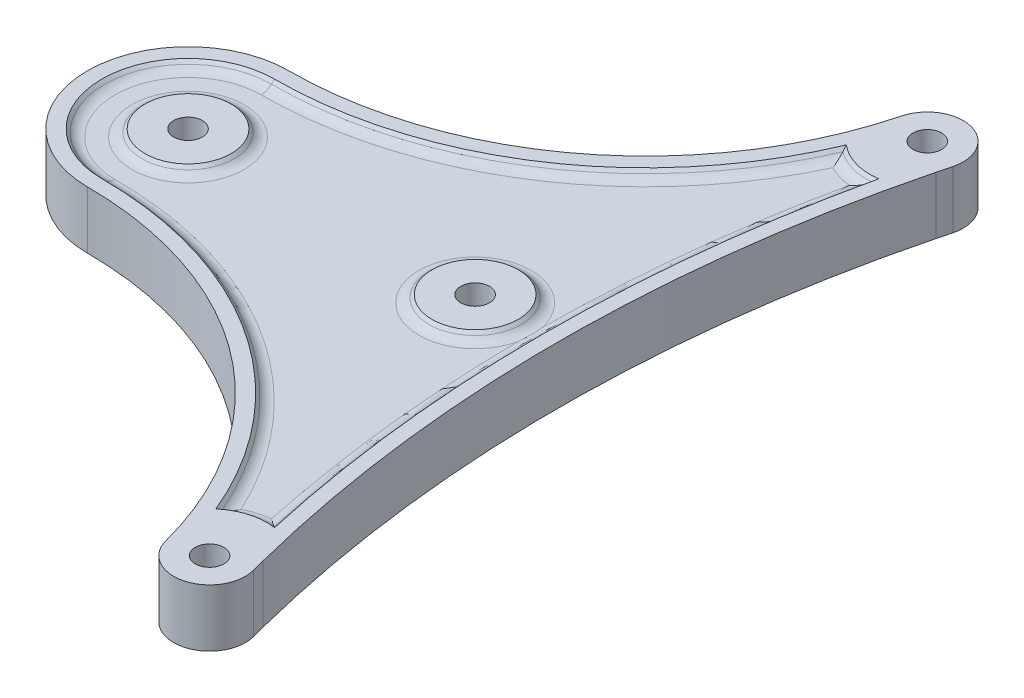
SolidWorks part; units mm, degrees
ref_plane "Front Plane" through (0, 0, 0) normal (0, 0, 1) x (1, 0, 0)
ref_plane "Top Plane" through (0, 0, 0) normal (0, 1, 0) x (1, 0, 0)
ref_plane "Right Plane" through (0, 0, 0) normal (1, 0, 0) x (0, 0, -1)
sketch "Sketch5" plane through (0, 0, 0) normal (0, 1, 0) x (1, 0, 0)
  line L0 (-10, 0) -> (3, 0) construction
  line L1 (3, -50) -> (3, 50) construction
  point P7 (3, 0)
  dimension "D1" = 13
  dimension "D2" = 100
  dimension "D3" = 3
sketch "Sketch1" plane through (0, 0, 0) normal (0, 1, 0) x (1, 0, 0)
  line L0 (3, -50) -> (-10, 0) construction
  line L7 (-1.8391, -51.2582) -> (-14.8391, -1.2582)
  line L8 (7.8391, -48.7418) -> (-5.1609, 1.2582)
  line L9 (3, 50) -> (-10, 0) construction
  line L10 (7.8391, 48.7418) -> (-5.1609, -1.2582)
  line L11 (-1.8391, 51.2582) -> (-14.8391, 1.2582)
  arc A0 (-1.8391, -51.2582) -> (7.8391, -48.7418) centre (3, -50) ccw
  arc A1 (-5.1609, 1.2582) -> (-14.8391, -1.2582) centre (-10, 0) ccw
  arc A2 (7.8391, 48.7418) -> (-1.8391, 51.2582) centre (3, 50) ccw
  arc A3 (-14.8391, 1.2582) -> (-5.1609, -1.2582) centre (-10, 0) ccw
  point P0 (0, 0)
  point P6 (-3.5, -25)
  point P13 (-3.5, 25)
  dimension "D3" = 5
extrude "Boss-Extrude1" add sketch "Sketch1" along normal mid plane 8 contours A3 L7 A0 L8 L10 | A1 A3 L10 L8 | L10 A2 L11 A1 L8 region at (-2.5112, 0, 28.8085) region at (-9.991, 0, 0) region at (-2.5112, 0, -28.8085)
sketch "Sketch2" plane through (0, 4, 0) normal (0, 1, 0) x (1, 0, 0)
  circle A0 centre (-10, 0) radius 2
  dimension "D1" = 4
extrude "Cut-Extrude1" cut sketch "Sketch2" against normal through all
sketch "Sketch4" plane through (0, 4, 0) normal (0, 1, 0) x (1, 0, 0)
  circle A0 centre (3, -50) radius 2
  circle A1 centre (3, 50) radius 2
  dimension "D1" = 4
extrude "Cut-Extrude2" cut sketch "Sketch4" against normal through all
sketch "Sketch6" plane through (0, 0, 0) normal (0, 1, 0) x (1, 0, 0)
  line L0 (3, 0) -> (-64.0179, 0) construction
  line L1 (-1.8391, -51.2582) -> (-14.8391, -1.2582) construction
  line L2 (-1.8391, 51.2582) -> (-14.8391, 1.2582) construction
  line L3 (-1.8391, -51.2582) -> (-14.8391, -1.2582)
  line L4 (-1.8391, 51.2582) -> (-14.8391, 1.2582)
  arc A0 (-50, 14.0179) -> (-50, -14.0179) centre (-50, 0) ccw
  arc A1 (-14.8391, 1.2582) -> (-14.8391, -1.2582) centre (-10, 0) ccw construction
  arc A2 (-1.8391, -51.2582) -> (-50, -14.0179) centre (-50, -63.78) ccw
  arc A4 (-1.8391, 51.2582) -> (-50, 14.0179) centre (-50, 63.78) cw
  arc A6 (-14.8391, 1.2582) -> (-14.8391, -1.2582) centre (-10, 0) ccw
  dimension "D1" = 50
extrude "Boss-Extrude2" add sketch "Sketch6" along normal mid plane 8 contours A6 L0 A0 A2 L3 | L0 A6 L4 A4 A0 | L0 A0 | A0 L0 region at (-31.4296, 0, 0)
sketch "Sketch7" plane through (0, 4, 0) normal (0, 1, 0) x (1, 0, 0)
  circle A0 centre (-50, 0) radius 2
  dimension "D1" = 4
extrude "Cut-Extrude3" cut sketch "Sketch7" against normal through all
sketch "Sketch8" plane through (0, 0, 0) normal (0, 1, 0) x (1, 0, 0)
  line L0 (7.8391, 48.7418) -> (-4.8338, 0) construction
  line L1 (7.8391, -48.7418) -> (-4.8338, 0) construction
  line L2 (7.8391, 48.7418) -> (-4.8338, 0)
  line L3 (7.8391, -48.7418) -> (-4.8338, 0)
  arc A0 (7.8391, -48.7418) -> (7.8391, 48.7418) centre (191.4807, 0) cw
  dimension "D1" = 190
extrude "Boss-Extrude3" add sketch "Sketch8" along normal mid plane 8 contours L3 A0 L2 region at (0.1904, 0, 0)
sketch "Sketch9" plane through (0, 4, 0) normal (0, 1, 0) x (1, 0, 0)
  line L2 (7.8391, -48.7418) -> (7.3545, -46.8778)
  line L3 (7.3545, 46.8778) -> (7.8391, 48.7418)
  arc A1 (7.0206, -45.5464) -> (-2.7315, -48.2251) centre (3, -50) ccw construction
  circle A2 centre (-50, 0) radius 6
  circle A3 centre (-50, 0) radius 6
  circle A4 centre (-10, 0) radius 6
  arc A5 (-2.7315, 48.2251) -> (7.0206, 45.5464) centre (3, 50) ccw construction
  arc A6 (7.8391, 48.7418) -> (-1.8391, 51.2582) centre (3, 50) ccw
  arc A7 (-50, 14.0179) -> (-1.8391, 51.2582) centre (-50, 63.78) ccw
  arc A8 (-50, 14.0179) -> (-1.8391, 51.2582) centre (-50, 63.78) ccw
  arc A10 (-1.8391, -51.2582) -> (7.8391, -48.7418) centre (3, -50) ccw
  arc A15 (-50, 14.0179) -> (-50, -14.0179) centre (-50, 0) ccw
  arc A16 (-50, 12.0179) -> (-50, -12.0179) centre (-50, 0) ccw
  arc A17 (-50, 14.0179) -> (-50, -14.0179) centre (-50, 0) ccw
  arc A18 (-50, 12.0179) -> (-2.1994, 43.92) centre (-50, 63.78) ccw
  arc A19 (-2.1994, 43.92) -> (4.1494, 42.083) centre (3, 50) ccw
  arc A20 (4.1494, 42.083) -> (4.1494, -42.083) centre (191.4807, 0) ccw
  arc A21 (-1.8391, -51.2582) -> (-50, -14.0179) centre (-50, -63.78) ccw
  arc A22 (4.1494, -42.083) -> (-2.1994, -43.92) centre (3, -50) ccw
  arc A23 (-1.8391, -51.2582) -> (-50, -14.0179) centre (-50, -63.78) ccw
  arc A25 (-2.1994, -43.92) -> (-50, -12.0179) centre (-50, -63.78) ccw
  arc A26 (4.1494, 42.083) -> (5.0789, -46.0258) centre (191.4807, 0) ccw construction
  arc A27 (7.3545, 46.8778) -> (7.3545, -46.8778) centre (191.4807, 0) ccw
  arc A28 (-0.8317, -47.6) -> (-50, -12.0179) centre (-50, -63.78) ccw construction
  arc A29 (7.3545, 46.8778) -> (7.3545, -46.8778) centre (191.4807, 0) ccw
  arc A32 (-50, 14.0179) -> (-2.7315, 48.2251) centre (-50, 63.78) ccw construction
  arc A33 (-50, 14.0179) -> (-50, -14.0179) centre (-50, 0) ccw construction
  arc A34 (-2.7315, -48.2251) -> (-50, -14.0179) centre (-50, -63.78) ccw construction
  arc A35 (7.0206, 45.5464) -> (7.0206, -45.5464) centre (191.4807, 0) ccw construction
  point P36 (8.3608, -44.0618)
  point P37 (-4.642, -47.6335)
  dimension "D1" = 0
  dimension "D2" = 4
  dimension "D3" = 2
extrude "Cut-Extrude4" cut sketch "Sketch9" against normal blind 1 draft 45 contours A25 A22 A20 A19 A18 A16 A4 A3 region at (-20.6977, 4, 0)
fillet "Fillet5" radius 2 8 edges at (-50, 3, 7) (-10, 3, 7) (-61.0179, 3, 0) (-21.2398, 3, -19.5455) (0.4606, 3, -41.3657) (-1.5193, 3, 0) (0.4606, 3, 41.3657) (-21.2398, 3, 19.5455)
mirror "Mirror2" about plane through (0, 0, 0) normal (0, 1, 0) of "Cut-Extrude4", "Fillet5"
